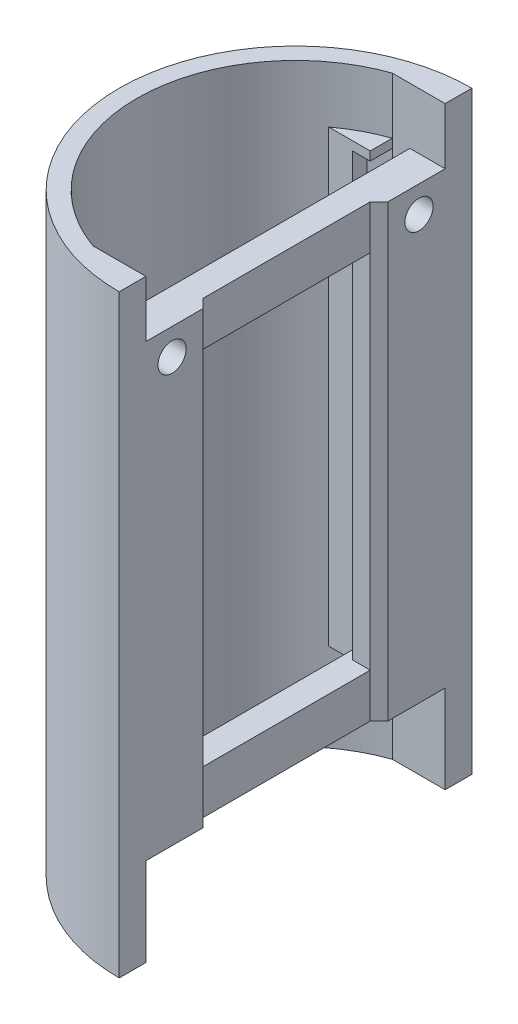
SolidWorks part; units mm, degrees
ref_plane "前视基准面" through (0, 0, 0) normal (0, 0, 1) x (1, 0, 0)
ref_plane "上视基准面" through (0, 0, 0) normal (0, 1, 0) x (1, 0, 0)
ref_plane "右视基准面" through (0, 0, 0) normal (1, 0, 0) x (0, 0, -1)
other "Configuration Table"
sketch "草图1" plane through (0, 0, 0) normal (0, 1, 0) x (1, 0, 0)
  line L0 (0, -473.638) -> (0, 23208.2609) construction
  line L1 (0, 0) -> (-4, 0) construction
  line L2 (0, 20) -> (0, -20)
  line L3 (-4, -17.5499) -> (-4, 17.5499)
  arc A0 (0, 20) -> (0, -20) centre (0, 0) ccw
  arc A1 (-4, 17.5499) -> (-4, -17.5499) centre (0, 0) ccw
  point P12 (-4, 0)
  dimension "D1" = 40
  dimension "D2" = 36
  dimension "D3" = 4
extrude "凸台-拉伸1" add sketch "草图1" along normal blind 70
sketch "草图3" plane through (0, 0, 0) normal (1, 0, 0) x (0, 0, -1)
  line L0 (-20, 0) -> (20, 0) construction
  line L1 (-16, 60) -> (16, 60) construction
  line L2 (-16, 60) -> (-16, 0) construction
  line L3 (-16, 0) -> (16, 0) construction
  line L4 (16, 60) -> (16, 0) construction
  line L5 (-20, 70) -> (20, 70) construction
  circle A0 centre (-14, 58) radius 2 construction
  circle A1 centre (14, 58) radius 2 construction
  circle A2 centre (-14, 58) radius 1
  circle A3 centre (14, 58) radius 1
  point P4 (0, 60)
  dimension "D4" = 4
  dimension "D5" = 4
  dimension "D6" = 2
  dimension "D7" = 2
  dimension "D1" = 0
  dimension "D2" = 10
  dimension "D3" = 32
extrude "切除-拉伸2" cut sketch "草图3" against normal up to surface (4 mm away) from surface up to face at (-4, 35, 0) starting at face at (0, 35, 0)
sketch "草图5" plane through (0, 0, 0) normal (0, 1, 0) x (1, 0, 0)
  line L0 (0, -1000) -> (0, 49000) construction
  line L1 (-1000, 0) -> (49000, 0) construction
  line L2 (-6, 16.9706) -> (6, 16.9706) construction
  line L3 (-6, -16.9706) -> (6, -16.9706) construction
  line L4 (0, 16.9706) -> (0, -16.9706)
  line L5 (0, -16.9706) -> (-4, -16.9706)
  line L6 (-4, -17.5499) -> (-4, 17.5499) construction
  line L7 (-4, -16.9706) -> (-4, 16.9706)
  line L8 (-4, 16.9706) -> (0, 16.9706)
  circle A0 centre (0, 0) radius 18 construction
  point P11 (0, 16.9706)
  dimension "D1" = 12
extrude "切除-拉伸4" cut sketch "草图5" against normal blind 9 from surface starting at face at (-10, 70, 0)
sketch "草图6" plane through (0, 0, 0) normal (0, 1, 0) x (1, 0, 0)
  line L0 (-4, 16.9706) -> (-6, 16.9706)
  line L1 (0, 16.9706) -> (0, 18)
  line L2 (-4, -16.9706) -> (-6, -16.9706)
  line L3 (0, -16.9706) -> (0, -18)
  line L4 (-4, 16.9706) -> (-4, -16.9706)
  line L5 (0, 16.9706) -> (-4, 16.9706)
  line L6 (0, -16.9706) -> (0, 16.9706)
  line L7 (-4, -16.9706) -> (0, -16.9706)
  line L9 (0, 16.9706) -> (-4, 16.9706)
  line L11 (-4, -16.9706) -> (0, -16.9706)
  arc A0 (0, 18) -> (-6, 16.9706) centre (0, 0) ccw
  arc A1 (-6, -16.9706) -> (0, -18) centre (0, 0) ccw
  dimension "D1" = 0
extrude "凸台-拉伸2" add sketch "草图6" against normal up to surface from surface up to face at (-10, 0, 0) starting at face at (-6.25, 70, 0)
sketch "草图7" plane through (0, 0, 0) normal (0, 1, 0) x (1, 0, 0)
  line L4 (-4, 16.9706) -> (-4, -16.9706)
  line L5 (0, 16.9706) -> (-4, 16.9706)
  line L6 (0, -16.9706) -> (0, 16.9706)
  line L7 (-4, -16.9706) -> (0, -16.9706)
  line L8 (-4, 16.9706) -> (-4, -16.9706)
  line L9 (0, 16.9706) -> (-4, 16.9706)
  line L10 (0, -16.9706) -> (0, 16.9706)
  line L11 (-4, -16.9706) -> (0, -16.9706)
  dimension "D1" = 0
extrude "切除-拉伸5" cut sketch "草图7" along normal blind 10
sketch "草图8" plane through (0, 0, 0) normal (0, 1, 0) x (1, 0, 0)
  line L0 (0, 16.9706) -> (0, -16.9706) construction
  line L1 (-6, 16.9706) -> (0, 16.9706)
  line L2 (-6, 16.9706) -> (-6, 14.4706)
  line L3 (-6, 14.4706) -> (0, 14.4706)
  line L4 (0, 16.9706) -> (0, 14.4706)
  line L6 (0, -16.9706) -> (-6, -16.9706)
  line L7 (0, -16.9706) -> (0, -14.4706)
  line L8 (0, -14.4706) -> (-6, -14.4706)
  line L9 (-6, -16.9706) -> (-6, -14.4706)
  dimension "D1" = 2.5
  dimension "D2" = 2.5
extrude "凸台-拉伸3" add sketch "草图8" against normal blind 1 from surface starting at face at (-2, 61, 0)
sketch "草图10" plane through (0, 0, 0) normal (0, 1, 0) x (1, 0, 0)
  line L0 (-6, 16.9706) -> (-6, 14.4706)
  line L1 (-6, 14.4706) -> (-10.7053, 14.4706)
  line L2 (-6, -14.4706) -> (-10.7053, -14.4706)
  line L3 (-6, -14.4706) -> (-6, -16.9706)
  arc A0 (-6, 16.9706) -> (-10.7053, 14.4706) centre (0, 0) ccw
  arc A1 (-10.7053, -14.4706) -> (-6, -16.9706) centre (0, 0) ccw
extrude "凸台-拉伸4" add sketch "草图10" along normal up to surface (70 mm away) from surface up to face at (-7.3333, 70, 0) starting at face at (-7.3333, 0, 0)
sketch "草图11" plane through (0, 0, 0) normal (0, 1, 0) x (1, 0, 0)
  line L0 (0, 16.9706) -> (0, -16.9706) construction
  line L1 (-6, 16.9706) -> (0, 16.9706)
  line L2 (-6, 16.9706) -> (-6, 14.4706)
  line L3 (-6, 14.4706) -> (0, 14.4706)
  line L4 (0, 16.9706) -> (0, 14.4706)
  line L5 (-6, 14.4706) -> (-10.7053, 14.4706) construction
  line L7 (-6, -14.4706) -> (0, -14.4706)
  line L8 (-6, -14.4706) -> (-6, -16.9706)
  line L9 (-6, -16.9706) -> (0, -16.9706)
  line L10 (0, -14.4706) -> (0, -16.9706)
  dimension "D1" = 0
extrude "凸台-拉伸5" add sketch "草图11" along normal up to surface (70 mm away) from surface up to face at (-7.2705, 70, 0) starting at face at (-4, 61, 0)
sketch "草图12" plane through (0, 0, 0) normal (0, 0, 1) x (1, 0, 0)
  line L1 (-6, 60) -> (-4, 60)
  line L2 (-6, 60) -> (-6, 61)
  line L3 (-6, 61) -> (-4, 61)
  line L4 (-4, 60) -> (-4, 61)
extrude "切除-拉伸6" cut sketch "草图12" against normal up to surface (16.9706 mm away) from surface up to face at (-3.3333, 23.3333, -16.9706) starting at face at (-3.3333, 23.3333, 16.9706)
sketch "草图14" plane through (0, 0, 0) normal (0, 1, 0) x (1, 0, 0)
  line L0 (-4, -14.4706) -> (-4, 14.4706) construction
  line L1 (-4, 10.4706) -> (-3, 10.4706)
  line L2 (-4, 10.4706) -> (-4, -10.4706)
  line L3 (-4, -10.4706) -> (-3, -10.4706)
  line L4 (-3, 10.4706) -> (-3, -10.4706)
  line L5 (-10.7053, -14.4706) -> (0, -14.4706) construction
  line L6 (-4, 14.4706) -> (0, 14.4706) construction
  line L7 (0, 14.4706) -> (0, -14.4706) construction
  line L8 (-1, 10.4706) -> (0, 10.4706)
  line L9 (-1, 10.4706) -> (-1, -10.4706)
  line L10 (-1, -10.4706) -> (0, -10.4706)
  line L11 (0, 10.4706) -> (0, -10.4706)
  line L12 (0, -14.4706) -> (-4, -14.4706) construction
  line L13 (0, 14.4706) -> (-10.7053, 14.4706) construction
  dimension "D1" = 1
  dimension "D2" = 4
  dimension "D3" = 4
  dimension "D4" = 1
  dimension "D5" = 4
  dimension "D6" = 4
extrude "切除-拉伸8" cut sketch "草图14" along normal up to surface (61 mm away) from surface up to face at (-2, 61, 0) starting at face at (-2, 10, 0)
sketch "草图15" plane through (0, 0, 0) normal (1, 0, 0) x (0, 0, -1)
  line L0 (10.4706, 61) -> (10.4706, 10) construction
  line L5 (-10.4706, 61) -> (-10.4706, 10) construction
  line L6 (10.4706, 61) -> (-10.4706, 61) construction
  line L7 (-10.4706, 10) -> (10.4706, 10) construction
  line L9 (-9.4706, 56) -> (9.4706, 56)
  line L10 (-9.4706, 56) -> (-9.4706, 15)
  line L11 (-9.4706, 15) -> (9.4706, 15)
  line L12 (9.4706, 56) -> (9.4706, 15)
  dimension "D1" = 1
  dimension "D2" = 1
  dimension "D3" = 5
  dimension "D4" = 5
extrude "切除-拉伸9" cut sketch "草图15" against normal up to surface (3 mm away) from surface up to face at (-3, 35.5, 0) starting at face at (-1, 35.5, 0)
sketch "草图17" plane through (0, 0, 0) normal (1, 0, 0) x (0, 0, -1)
  circle A0 centre (-14, 58) radius 1.6
  circle A1 centre (14, 58) radius 1.6
  dimension "D1" = 3.2
  dimension "D2" = 3.2
extrude "切除-拉伸10" cut sketch "草图17" against normal blind 2.5
sketch "草图20" plane through (0, 0, 0) normal (0, 1, 0) x (1, 0, 0)
  line L0 (-1, 10.4706) -> (0, 10.4706)
  line L1 (0, 14.4706) -> (0, 10.4706) construction
  line L2 (0, 10.4706) -> (-1, 10.4706) construction
  line L3 (0, 10.4706) -> (-1, 9.4706)
  line L4 (-1, 10.4706) -> (-1, -10.4706) construction
  line L5 (-1, 9.4706) -> (-1, 10.4706)
  line L6 (-4, 10.4706) -> (-3, 10.4706)
  line L7 (-3, 10.4706) -> (-3, 9.4706)
  line L8 (-3, -10.4706) -> (-3, 10.4706) construction
  line L9 (-3, 9.4706) -> (-4, 10.4706)
  line L10 (-4, -10.4706) -> (-3, -10.4706)
  line L11 (-3, -10.4706) -> (-3, -9.4706)
  line L12 (-3, -9.4706) -> (-4, -10.4706)
  line L13 (0, -10.4706) -> (-1, -10.4706)
  line L14 (-1, -10.4706) -> (0, -10.4706) construction
  line L15 (-1, -10.4706) -> (-1, -9.4706)
  line L16 (-1, -9.4706) -> (0, -10.4706)
  dimension "D1" = 1
  dimension "D2" = 1
  dimension "D3" = 1
  dimension "D4" = 1
  dimension "D5" = 1
extrude "凸台-拉伸11" add sketch "草图20" against normal up to surface (-10 mm away) from surface up to face at (-2, 10, 0) starting at face at (-2, 61, 0)
sketch "草图21" plane through (0, 0, 0) normal (0, 1, 0) x (1, 0, 0)
  line L0 (-4, 10.4706) -> (-4, -10.4706)
  line L1 (-4, -10.4706) -> (-3, -9.4706)
  line L2 (-3, -9.4706) -> (-3, 9.4706)
  line L3 (-3, 9.4706) -> (-4, 10.4706)
extrude "凸台-拉伸12" add sketch "草图21" against normal up to surface (-56 mm away) from surface up to face at (-2, 56, 0) starting at face at (-2, 61, 0)
sketch "草图22" plane through (0, 0, 0) normal (0, 1, 0) x (1, 0, 0)
  line L4 (-4, 10.4706) -> (-4, -10.4706)
  line L5 (-4, -10.4706) -> (-3, -9.4706)
  line L6 (-3, -9.4706) -> (-3, 9.4706)
  line L7 (-3, 9.4706) -> (-4, 10.4706)
  line L8 (-4, 10.4706) -> (-4, -10.4706)
  line L9 (-4, -10.4706) -> (-3, -9.4706)
  line L10 (-3, -9.4706) -> (-3, 9.4706)
  line L11 (-3, 9.4706) -> (-4, 10.4706)
  dimension "D1" = 0
extrude "凸台-拉伸13" add sketch "草图22" along normal up to surface (15 mm away) from surface up to face at (-2, 15, 0) starting at face at (-2, 10, 0)
sketch "草图23" plane through (0, 0, 0) normal (0, 0, 1) x (1, 0, 0)
  line L0 (-3, 56) -> (-1, 56) construction
  line L1 (-6, 61) -> (-8, 61)
  line L2 (-6, 61) -> (-6, 55)
  line L3 (-6, 55) -> (-8, 55)
  line L4 (-8, 61) -> (-8, 55)
  dimension "D1" = 1
  dimension "D2" = 2
extrude "切除-拉伸11" cut sketch "草图23" along normal up to surface (1.654 mm away) from surface up to face at (-14.3526, 35, 0) starting at face at (-5.3444, 46.1429, 14.4706)
sketch "草图24" plane through (0, 0, 0) normal (0, 0, 1) x (1, 0, 0)
  line L4 (-6, 61) -> (-8, 61)
  line L5 (-8, 61) -> (-8, 55)
  line L6 (-8, 55) -> (-6, 55)
  line L7 (-6, 55) -> (-6, 61)
  line L8 (-6, 61) -> (-8, 61)
  line L9 (-8, 61) -> (-8, 55)
  line L10 (-8, 55) -> (-6, 55)
  line L11 (-6, 55) -> (-6, 61)
  dimension "D1" = 0
extrude "切除-拉伸12" cut sketch "草图24" against normal up to surface (16.1245 mm away) up to face at (-14.3526, 35, 0)
sketch "草图25" plane through (0, 0, 0) normal (0, 1, 0) x (1, 0, 0)
  line L0 (-6, -16.9706) -> (-6, -14.4706)
  line L1 (-8, -14.4706) -> (-4, -14.4706) construction
  line L2 (-6, -14.4706) -> (-10.7053, -14.4706)
  line L3 (-10.7053, 14.4706) -> (-6, 14.4706)
  line L4 (-4, 14.4706) -> (-8, 14.4706) construction
  line L5 (-6, 14.4706) -> (-6, 16.9706)
  arc A0 (-10.7053, -14.4706) -> (-6, -16.9706) centre (0, 0) ccw
  arc A1 (-6, 16.9706) -> (-10.7053, 14.4706) centre (0, 0) ccw
extrude "切除-拉伸13" cut sketch "草图25" along normal up to surface (10 mm away) from surface up to face at (-1.25, 10, 0) starting at face at (-7.2705, 0, 0)
sketch "草图29" plane through (0, 0, 0) normal (0, 1, 0) x (1, 0, 0)
  line L0 (0, -16.9706) -> (0, -14.4706)
  line L1 (0, -14.4706) -> (-10.7053, -14.4706)
  line L2 (0, -16.9706) -> (-6, -16.9706)
  line L3 (-4, -16.9706) -> (-6, -16.9706)
  line L4 (0, -18) -> (0, -16.9706)
  line L5 (0, -16.9706) -> (-4, -16.9706)
  line L6 (-4, -16.9706) -> (-6, -16.9706) construction
  line L8 (0, -16.9706) -> (-4, -16.9706) construction
  line L9 (-6, 16.9706) -> (-4, 16.9706)
  line L10 (0, 16.9706) -> (0, 18)
  line L11 (-4, 16.9706) -> (0, 16.9706)
  line L12 (-6, 16.9706) -> (-4, 16.9706) construction
  line L14 (-4, 16.9706) -> (0, 16.9706) construction
  line L15 (-6, 16.9706) -> (0, 16.9706)
  line L16 (0, 16.9706) -> (0, 14.4706)
  line L17 (0, 14.4706) -> (-10.7053, 14.4706)
  arc A0 (-10.7053, -14.4706) -> (-6, -16.9706) centre (0, 0) ccw
  arc A1 (-6, -16.9706) -> (0, -18) centre (0, 0) ccw
  arc A3 (0, 18) -> (-6, 16.9706) centre (0, 0) ccw
  arc A5 (-6, 16.9706) -> (-10.7053, 14.4706) centre (0, 0) ccw
  dimension "D1" = 0
  dimension "D2" = 0
extrude "切除-拉伸18" cut sketch "草图29" against normal up to surface (-61 mm away) from surface up to face at (-1.25, 61, 0) starting at face at (-8.1175, 70, 0)
sketch "草图30" plane through (0, 0, 0) normal (0, 1, 0) x (1, 0, 0)
  line L0 (-8, 16.1245) -> (-8, 14.4706)
  line L1 (-8, 14.4706) -> (-4, 14.4706)
  line L2 (-4, -16.9706) -> (-4, 16.9706) construction
  line L3 (-4, 14.4706) -> (-4, 16.9706)
  line L4 (-6, 16.9706) -> (0, 16.9706) construction
  line L5 (-4, 16.9706) -> (-6, 16.9706)
  line L6 (-8, -16.1245) -> (-8, -14.4706)
  line L7 (-8, -14.4706) -> (-4, -14.4706)
  line L8 (-4, -14.4706) -> (-4, -16.9706)
  line L9 (-4, -16.9706) -> (-6, -16.9706)
  arc A0 (-6, 16.9706) -> (-8, 16.1245) centre (0, 0) ccw
  arc A1 (-8, -16.1245) -> (-6, -16.9706) centre (0, 0) ccw
extrude "凸台-拉伸16" add sketch "草图30" against normal blind 1 from surface starting at face at (-8.9139, 61, -15.0418)
sketch "草图31" plane through (0, 0, 0) normal (0, 1, 0) x (1, 0, 0)
  line L4 (0, -20) -> (0, -16.9706)
  line L5 (0, -16.9706) -> (-6, -16.9706)
  line L6 (-6, 16.9706) -> (0, 16.9706)
  line L7 (0, 16.9706) -> (0, 20)
  line L8 (0, -20) -> (0, -16.9706)
  line L9 (0, -16.9706) -> (-6, -16.9706)
  line L10 (-6, 16.9706) -> (0, 16.9706)
  line L11 (0, 16.9706) -> (0, 20)
  arc A2 (-6, 16.9706) -> (-6, -16.9706) centre (0, 0) ccw
  arc A3 (0, 20) -> (0, -20) centre (0, 0) ccw
  arc A4 (-6, 16.9706) -> (-6, -16.9706) centre (0, 0) ccw
  arc A5 (0, 20) -> (0, -20) centre (0, 0) ccw
  dimension "D1" = 0
extrude "凸台-拉伸17" add sketch "草图31" along normal blind 2.4 from surface starting at face at (-7.3333, 70, 0)
sketch "草图32" plane through (0, 0, 0) normal (0, 1, 0) x (1, 0, 0)
  line L4 (0, 16.9706) -> (0, 20)
  line L5 (0, -20) -> (0, -16.9706)
  line L6 (0, -16.9706) -> (-6, -16.9706)
  line L7 (-6, 16.9706) -> (0, 16.9706)
  line L8 (0, 16.9706) -> (0, 20)
  line L9 (0, -20) -> (0, -16.9706)
  line L10 (0, -16.9706) -> (-6, -16.9706)
  line L11 (-6, 16.9706) -> (0, 16.9706)
  arc A2 (0, 20) -> (0, -20) centre (0, 0) ccw
  arc A3 (-6, 16.9706) -> (-6, -16.9706) centre (0, 0) ccw
  arc A4 (0, 20) -> (0, -20) centre (0, 0) ccw
  arc A5 (-6, 16.9706) -> (-6, -16.9706) centre (0, 0) ccw
  dimension "D1" = 0
extrude "切除-拉伸19" cut sketch "草图32" against normal blind 5 from surface starting at face at (-7.3333, 72.4, 0)
sketch "草图33" plane through (0, 0, 0) normal (0, 1, 0) x (1, 0, 0)
  line L1 (-6, -16.9706) -> (-4, -16.9706)
  line L2 (-6, -16.9706) -> (-6, 16.9706)
  line L3 (-6, 16.9706) -> (-4, 16.9706)
  line L4 (-4, -16.9706) -> (-4, 16.9706)
extrude "切除-拉伸20" cut sketch "草图33" along normal up to surface (61 mm away) from surface up to face at (-3.633, 61, 0) starting at face at (-7.3333, 0, 0)
